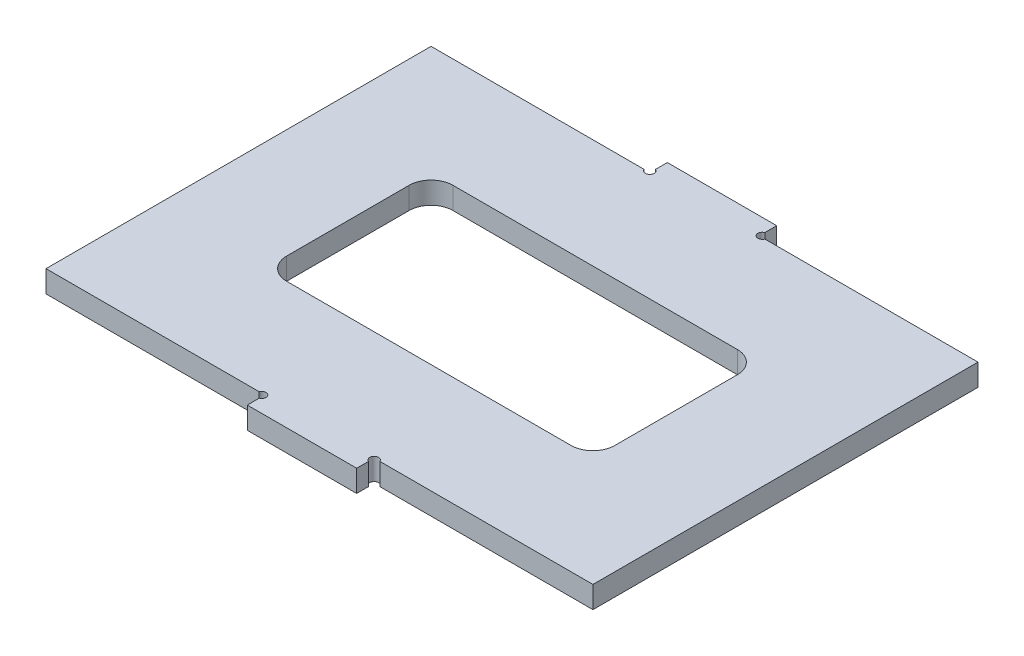
SolidWorks part; units mm, degrees
ref_plane "Front Plane" through (0, 0, 0) normal (0, 0, 1) x (1, 0, 0)
ref_plane "Top Plane" through (0, 0, 0) normal (0, 1, 0) x (1, 0, 0)
ref_plane "Right Plane" through (0, 0, 0) normal (1, 0, 0) x (0, 0, -1)
sketch "Sketch1" plane through (0, 0, 0) normal (0, 1, 0) x (1, 0, 0)
  line L1 (-125, 88) -> (125, 88)
  line L2 (-125, 88) -> (-125, -88)
  line L3 (-125, -88) -> (125, -88)
  line L4 (125, 88) -> (125, -88)
  line L5 (-125, 88) -> (125, -88) construction
  line L6 (-125, -88) -> (125, 88) construction
  point P0 (0, 0)
  dimension "D1" = 176
  dimension "D2" = 250
base flange "Base-Flange1" sketch "Sketch1" thickness 10 reverse thickness direction no parameters "D1"=6.2
sketch "Sketch6" plane through (0, 0, 0) normal (0, 1, 0) x (1, 0, 0)
  line L0 (125, 88) -> (-125, 88) construction
  line L1 (-25, 88) -> (25, 88)
  line L2 (-25, 88) -> (-25, 96)
  line L3 (-25, 96) -> (25, 96)
  line L4 (25, 88) -> (25, 96)
  line L5 (0, 88) -> (0, 0) construction
  line L6 (0, 0) -> (-125, 0) construction
  line L7 (-125, 88) -> (-125, -88) construction
  line L8 (25, -88) -> (25, -96)
  line L9 (-25, -96) -> (25, -96)
  line L10 (-25, -88) -> (-25, -96)
  line L11 (-25, -88) -> (25, -88)
  dimension "D1" = 50
  dimension "D2" = 8
extrude "Boss-Extrude1" add sketch "Sketch6" against normal blind 10
sketch "Sketch7" plane through (0, 0, 0) normal (0, 1, 0) x (1, 0, 0)
  line L0 (25.7071, 88.7071) -> (25, 88) construction
  line L1 (125, 88) -> (25, 88) construction
  line L2 (0, 96) -> (0, 0) construction
  line L3 (25, 96) -> (-25, 96) construction
  line L4 (0, 0) -> (65.3646, 0) construction
  line L5 (-25.7071, 88.7071) -> (-25, 88) construction
  line L6 (-25.7071, -88.7071) -> (-25, -88) construction
  line L7 (25.7071, -88.7071) -> (25, -88) construction
  circle A0 centre (25.7071, 88.7071) radius 2
  circle A1 centre (-25.7071, 88.7071) radius 2
  circle A2 centre (-25.7071, -88.7071) radius 2
  circle A3 centre (25.7071, -88.7071) radius 2
  dimension "D1" = 45
  dimension "D3" = 4
  dimension "D2" = 1
extrude "Cut-Extrude1" cut sketch "Sketch7" against normal through all normal cut yes
sketch "Sketch8" plane through (0, 0, 0) normal (0, 1, 0) x (1, 0, 0)
  line L0 (-125, 88) -> (-125, -88) construction
  line L1 (75, 38) -> (-75, 38)
  line L2 (75, 38) -> (75, -38)
  line L3 (75, -38) -> (-75, -38)
  line L4 (-75, 38) -> (-75, -38)
  line L5 (75, 38) -> (-75, -38) construction
  line L6 (75, -38) -> (-75, 38) construction
  line L7 (-27.5779, 88) -> (-125, 88) construction
  point P0 (0, 0)
  dimension "D1" = 50
  dimension "D2" = 50
extrude "Cut-Extrude2" cut sketch "Sketch8" against normal through all normal cut yes
fillet "Fillet1" radius 10 4 edges at (75, -5, -38) (75, -5, 38) (-75, -5, 38) (-75, -5, -38)
sketch "Bend-Lines1" [suppressed] plane through (0, 0, 0) normal (0, 1, 0) x (1, 0, 0)
sketch "Bounding-Box1" [suppressed] plane through (0, 0, 0) normal (0, 1, 0) x (1, 0, 0)
sheet metal parameters "Sheet-Metal1" thickness 10 parameters "D1"=6.2
flat pattern "Flat-Pattern1" [suppressed]
sketch "Bend-Lines2" plane through (0, 0, 0) normal (0, 1, 0) x (1, 0, 0)
sketch3d "Bounding-Box2" [suppressed]
  line L0 (-125, -88, 0) -> (125, -88, 0) construction
  line L1 (-125, 88, 0) -> (125, 88, 0) construction
  line L2 (-125, -88, 0) -> (-125, 88, 0) construction
  line L3 (125, -88, 0) -> (125, 88, 0) construction
sheet metal parameters "Sheet-Metal2" thickness 10 parameters "D1"=6.2
flat pattern "Flat-Pattern1"
sketch "Bend-Lines2" plane through (0, 0, 0) normal (0, 1, 0) x (1, 0, 0)
sketch3d "Bounding-Box2" [suppressed]
  line L0 (125, -96, 0) -> (-125, -96, 0) construction
  line L1 (125, 96, 0) -> (-125, 96, 0) construction
  line L2 (125, -96, 0) -> (125, 96, 0) construction
  line L3 (-125, -96, 0) -> (-125, 96, 0) construction
sheet metal parameters "Sheet-Metal3" thickness 10 parameters "D1"=6.2
flat pattern "Flat-Pattern1"
sketch "Bend-Lines2" plane through (0, 0, 0) normal (0, 1, 0) x (1, 0, 0)
sketch3d "Bounding-Box2" [suppressed]
  line L0 (125, -96, 0) -> (-125, -96, 0) construction
  line L1 (125, 96, 0) -> (-125, 96, 0) construction
  line L2 (125, -96, 0) -> (125, 96, 0) construction
  line L3 (-125, -96, 0) -> (-125, 96, 0) construction
sheet metal parameters "Sheet-Metal4" thickness 10 parameters "D1"=6.2
flat pattern "Flat-Pattern1"
sketch "Bend-Lines2" plane through (0, 0, 0) normal (0, 1, 0) x (1, 0, 0)
sketch3d "Bounding-Box2" [suppressed]
  line L0 (125, -96, 0) -> (-125, -96, 0) construction
  line L1 (125, 96, 0) -> (-125, 96, 0) construction
  line L2 (125, -96, 0) -> (125, 96, 0) construction
  line L3 (-125, -96, 0) -> (-125, 96, 0) construction
